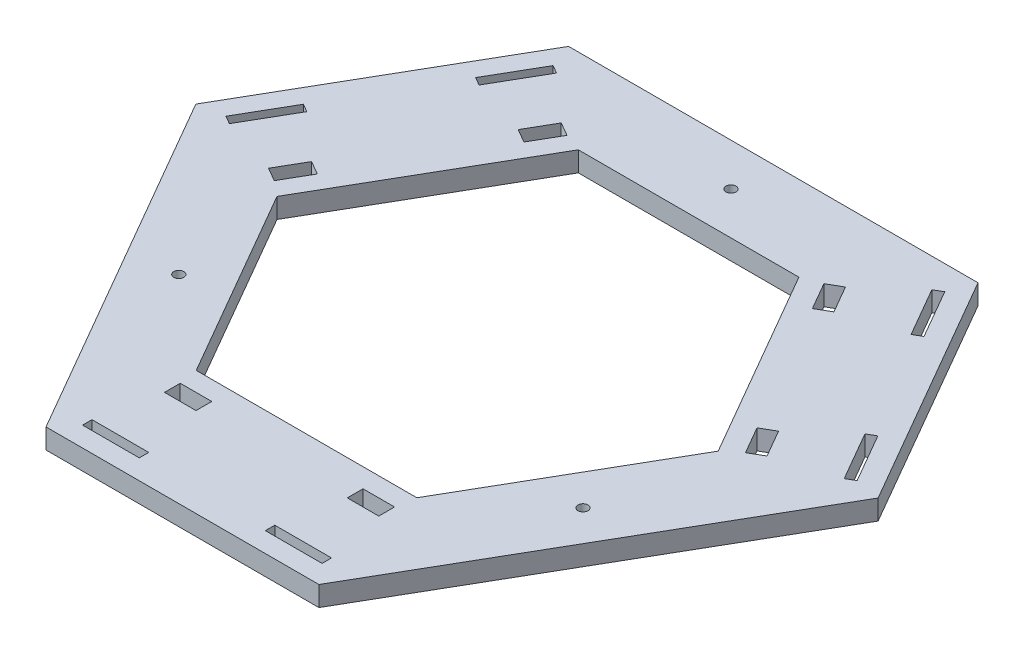
SolidWorks part; units mm, degrees
ref_plane "Front Plane" through (0, 0, 0) normal (0, 0, 1) x (1, 0, 0)
ref_plane "Top Plane" through (0, 0, 0) normal (0, 1, 0) x (1, 0, 0)
ref_plane "Right Plane" through (0, 0, 0) normal (1, 0, 0) x (0, 0, -1)
sketch "Sketch1" plane through (0, 0, 0) normal (0, 1, 0) x (1, 0, 0)
  line L0 (0, 200) -> (-173.2051, -100)
  line L1 (-173.2051, -100) -> (173.2051, -100)
  line L2 (173.2051, -100) -> (0, 200)
  line L4 (0, -175) -> (151.5544, 87.5)
  line L5 (151.5544, 87.5) -> (-151.5544, 87.5)
  line L6 (-151.5544, 87.5) -> (0, -175)
  circle A0 centre (0, 0) radius 200 construction
  circle A1 centre (0, 0) radius 100 construction
  circle A2 centre (0, 0) radius 175 construction
  circle A3 centre (0, 0) radius 87.5 construction
  dimension "D1" = 400
  dimension "D2" = 350
other "AlignGroup1"
extrude "Boss-Extrude1" add sketch "Sketch1" along normal blind 6.35 contours L0 L6 L1 L4 L2 L5 region at (0, 0, 0)
sketch "Sketch2" plane through (0, 6.35, 0) normal (0, 1, 0) x (1, 0, 0)
  line L0 (-43.3013, -100) -> (43.3013, -100) construction
  line L1 (-38, -90.7) -> (-20, -90.7)
  line L2 (-38, -90.7) -> (-38, -93.7)
  line L3 (-38, -93.7) -> (-20, -93.7)
  line L4 (-20, -90.7) -> (-20, -93.7)
  line L5 (0, -100) -> (0, 87.5) construction
  line L6 (64.9519, 87.5) -> (-64.9519, 87.5) construction
  line L7 (38, -90.7) -> (38, -93.7)
  line L8 (-86.6025, 50) -> (75.7772, -43.75) construction
  line L9 (-62.1466, 79.759) -> (-59.5485, 78.259)
  line L10 (20, -90.7) -> (20, -93.7)
  line L11 (-62.1466, 79.759) -> (-71.1466, 64.1705)
  line L12 (-71.1466, 64.1705) -> (-68.5485, 62.6705)
  line L13 (38, -93.7) -> (20, -93.7)
  line L14 (38, -90.7) -> (20, -90.7)
  line L15 (-59.5485, 78.259) -> (-68.5485, 62.6705)
  line L16 (-64.9519, 87.5) -> (-108.2532, 12.5) construction
  line L17 (43.3013, -100) -> (108.2532, 12.5) construction
  line L18 (-97.5485, 12.441) -> (-88.5485, 28.0295)
  line L19 (-91.1466, 29.5295) -> (-88.5485, 28.0295)
  line L20 (-100.1466, 13.941) -> (-91.1466, 29.5295)
  line L21 (-100.1466, 13.941) -> (-97.5485, 12.441)
  line L22 (86.6025, 50) -> (-75.7772, -43.75) construction
  line L23 (108.2532, 12.5) -> (64.9519, 87.5) construction
  line L24 (-108.2532, 12.5) -> (-43.3013, -100) construction
  line L25 (100.1466, 13.941) -> (91.1466, 29.5295)
  line L26 (59.5485, 78.259) -> (62.1466, 79.759)
  line L27 (59.5485, 78.259) -> (68.5485, 62.6705)
  line L28 (68.5485, 62.6705) -> (71.1466, 64.1705)
  line L29 (62.1466, 79.759) -> (71.1466, 64.1705)
  line L30 (88.5485, 28.0295) -> (91.1466, 29.5295)
  line L31 (97.5485, 12.441) -> (88.5485, 28.0295)
  line L32 (97.5485, 12.441) -> (100.1466, 13.941)
  line L33 (-24, -71.7) -> (-24, -66.7)
  line L34 (34, -71.7) -> (24, -71.7)
  line L35 (34, -71.7) -> (34, -66.7)
  line L36 (34, -66.7) -> (24, -66.7)
  line L37 (24, -71.7) -> (24, -66.7)
  line L38 (-34, -66.7) -> (-24, -66.7)
  line L39 (-34, -71.7) -> (-34, -66.7)
  line L40 (-34, -71.7) -> (-24, -71.7)
  line L41 (79.094, 6.4051) -> (74.094, 15.0654)
  line L42 (40.7639, 62.7949) -> (45.094, 65.2949)
  line L43 (40.7639, 62.7949) -> (45.7639, 54.1346)
  line L44 (45.7639, 54.1346) -> (50.094, 56.6346)
  line L45 (45.094, 65.2949) -> (50.094, 56.6346)
  line L46 (69.7639, 12.5654) -> (74.094, 15.0654)
  line L47 (74.7639, 3.9051) -> (69.7639, 12.5654)
  line L48 (74.7639, 3.9051) -> (79.094, 6.4051)
  line L49 (-74.7639, 3.9051) -> (-69.7639, 12.5654)
  line L50 (-45.094, 65.2949) -> (-40.7639, 62.7949)
  line L51 (-45.094, 65.2949) -> (-50.094, 56.6346)
  line L52 (-50.094, 56.6346) -> (-45.7639, 54.1346)
  line L53 (-40.7639, 62.7949) -> (-45.7639, 54.1346)
  line L54 (-74.094, 15.0654) -> (-69.7639, 12.5654)
  line L55 (-79.094, 6.4051) -> (-74.094, 15.0654)
  line L56 (-79.094, 6.4051) -> (-74.7639, 3.9051)
  point P4 (-29, -93.7)
  point P50 (29, -71.7)
  point P51 (29, -90.7)
  point P60 (64.0485, 70.4647)
  point P61 (47.594, 60.9647)
  point P70 (-47.594, 60.9647)
  dimension "D1" = 18
  dimension "D2" = 3
  dimension "D3" = 6.3
  dimension "D5" = 6.3
  dimension "D6" = 18
  dimension "D7" = 3
  dimension "D9" = 18
  dimension "D10" = 3
  dimension "D12" = 6.3
  dimension "D13" = 5
  dimension "D14" = 10
  dimension "D15" = 19
  dimension "D16" = 5
  dimension "D17" = 10
  dimension "D18" = 19
  dimension "D19" = 9
  dimension "D20" = 5
  dimension "D21" = 10
  dimension "D22" = 19
  dimension "D23" = 9
  dimension "D8" = 38
  dimension "D11" = 38
  dimension "D4" = 38
extrude "Cut-Extrude1" cut sketch "Sketch2" against normal through all
sketch "Sketch3" plane through (0, 6.35, 0) normal (0, 1, 0) x (1, 0, 0)
  point P0 (0, 0)
ref_axis "Axis1" through (0, 0, 0) along (0, 1, 0)
sketch "Sketch4" plane through (0, 6.35, 0) normal (0, 1, 0) x (1, 0, 0)
  line L0 (-30, 52.5) -> (30, 52.5) construction
  line L1 (30, 52.5) -> (30, -52.5) construction
  line L2 (30, -52.5) -> (-30, -52.5) construction
  line L3 (-30, -52.5) -> (-30, 52.5) construction
  line L5 (35, -60.6218) -> (70, 0)
  line L6 (70, 0) -> (35, 60.6218)
  line L7 (35, 60.6218) -> (-35, 60.6218)
  line L8 (-35, 60.6218) -> (-70, 0)
  line L9 (-70, 0) -> (-35, -60.6218)
  line L10 (-35, -60.6218) -> (35, -60.6218)
  circle A0 centre (0, 0) radius 60.6218 construction
  point P4 (0, 52.5)
  point P6 (-30, 0)
  dimension "D1" = 60
  dimension "D2" = 105
  dimension "D3" = 70
extrude "Cut-Extrude2" cut sketch "Sketch4" against normal through all
hole_wizard "Ø3.0mm Dowel Hole1" positions "Sketch5" profile "Sketch6" hole size "Ø3.0" standard "AS" end condition through all
sketch "Sketch5" plane through (0, 6.35, 0) normal (0, 1, 0) x (1, 0, 0)
  line L0 (0, 87.5) -> (0, 60.6218) construction
  line L1 (64.9519, 87.5) -> (-64.9519, 87.5) construction
  line L2 (35, 60.6218) -> (-35, 60.6218) construction
  line L4 (-52.5, -30.3109) -> (-75.7772, -43.75) construction
  line L5 (-70, 0) -> (-35, -60.6218) construction
  line L6 (-108.2532, 12.5) -> (-43.3013, -100) construction
  line L8 (35, -60.6218) -> (70, 0) construction
  line L9 (43.3013, -100) -> (108.2532, 12.5) construction
  line L10 (52.5, -30.3109) -> (75.7772, -43.75) construction
  point P37 (-64.1386, -37.0304)
  point P39 (64.1386, -37.0304)
  point P43 (0, 74.0609)
sketch "Sketch6" plane through (0, 6.35, -74.0609) normal (1, 0, 0) x (0, 0, 1)
  line L0 (0, 0) -> (0, 6.35)
  line L1 (0, 6.35) -> (1.6, 6.35)
  line L2 (1.6, 6.35) -> (1.6, 0)
  line L5 (1.6, 0) -> (0, 0)
  line L11 (0, -6.35) -> (0, 107.95) construction
  dimension "Thru Hole Dia." = 3.2
  dimension "Thru Hole Depth" = 6.35
equation "\"D19@Sketch2\"=\"D9@Sketch2\"/2"
equation "\"D23@Sketch2\"=\"D6@Sketch2\"/2"
